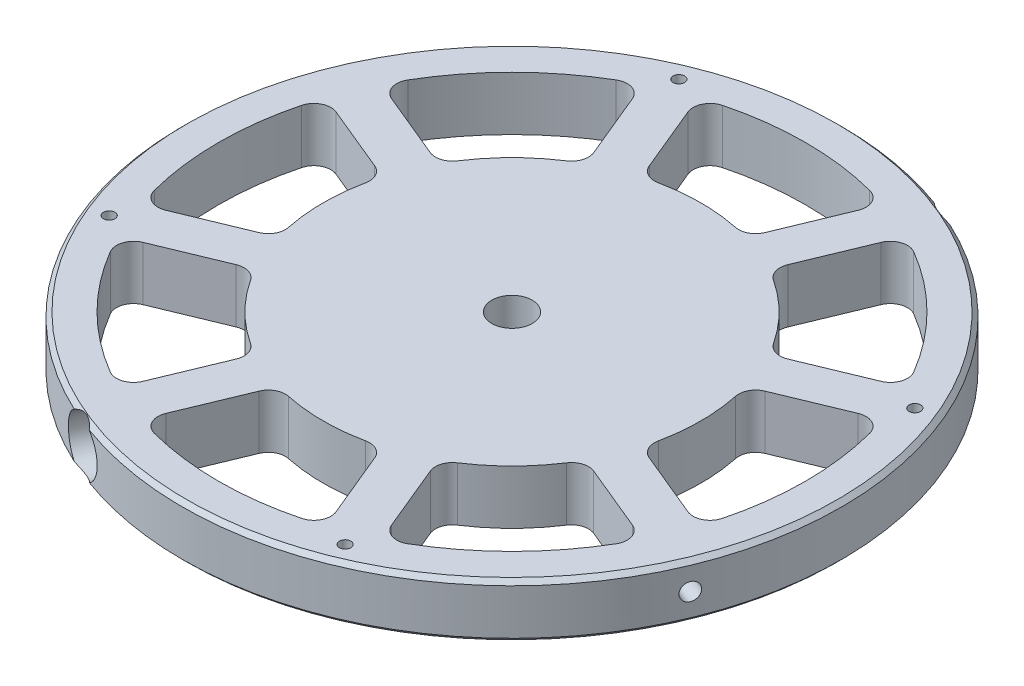
SolidWorks part; units mm, degrees
material "6061-T6 (SS)"
ref_plane "Front Plane" through (0, 0, 0) normal (0, 0, 1) x (1, 0, 0)
ref_plane "Top Plane" through (0, 0, 0) normal (0, 1, 0) x (1, 0, 0)
ref_plane "Right Plane" through (0, 0, 0) normal (1, 0, 0) x (0, 0, -1)
sketch "Sketch2" plane through (0, 0, 0) normal (1, 0, 0) x (0, 0, -1)
  line L0 (0, 0) -> (-77.55, 0)
  line L1 (-77.55, 0) -> (-77.55, 12.7)
  line L2 (-77.55, 12.7) -> (0, 12.7)
  line L5 (0, 12.7) -> (0, 0)
  dimension "D1" = 77.55
  dimension "D2" = 12.7
ref_axis "Axis1" through (0, -0.75, 0) along (0, 1, 0)
revolve "Revolve1" add sketch "Sketch2" angle 360 about axis through (0, -0.75, 0) along (0, 1, 0)
hole_wizard "#6-32 Tapped Hole2" positions "Sketch6" profile "Sketch7" tap size "#6-32" standard "ANSI Inch" end condition through all
sketch "Sketch6" plane through (0, 12.7, 0) normal (0, 1, 0) x (1, 0, 0)
  line L0 (0, 0) -> (-53.438, 129.0108) construction
  line L2 (0, 0) -> (0, 109.0908) construction
  point P0 (-27.7637, 67.0275)
  dimension "D1" = 22.5
  dimension "D2" = 72.55
sketch "Sketch7" plane through (-27.7637, 12.7, -67.0275) normal (1, 0, 0) x (0, 0, 1)
  line L0 (0, 0) -> (0, 12.7)
  line L1 (0, 12.7) -> (1.3525, 12.7)
  line L2 (1.3525, 12.7) -> (1.3525, 0)
  line L5 (1.3525, 0) -> (0, 0)
  line L11 (0, -6.35) -> (0, 107.95) construction
  dimension "Thread Major Dia." = 2.7051
  dimension "Thru Tap Drill Depth" = 12.7
pattern_circular "CirPattern3" count 4 over 360 about axis through (0, -0.75, 0) along (0, 1, 0) of "#6-32 Tapped Hole2"
sketch "Sketch8" plane through (0, 12.7, 0) normal (0, 1, 0) x (1, 0, 0)
  line L4 (0, 0) -> (0, 93.9995) construction
  line L5 (0, 0) -> (113.8372, 0) construction
  line L6 (-12.2829, 42.7192) -> (-21.7355, 65.5398)
  line L7 (12.2829, 42.7192) -> (21.7355, 65.5398)
  line L8 (0, 0) -> (-27.7637, 67.0275) construction
  arc A0 (-12.2829, 42.7192) -> (12.2829, 42.7192) centre (0, 0) cw
  arc A1 (-21.7355, 65.5398) -> (21.7355, 65.5398) centre (0, 0) cw
  circle A2 centre (0, 0) radius 77.55 construction
  dimension "D1" = 44.45
  dimension "D2" = 8.5
  dimension "D3" = 5
extrude "Cut-Extrude1" cut sketch "Sketch8" against normal through all
fillet "Fillet1" radius 4 4 edges at (12.2829, 6.35, -42.7192) (21.7355, 6.35, -65.5398) (-12.2829, 6.35, -42.7192) (-21.7355, 6.35, -65.5398)
pattern_circular "CirPattern4" count 8 over 360 about axis through (0, -0.75, 0) along (0, 1, 0) of "Cut-Extrude1", "Fillet1"
chamfer "Chamfer1" distance 1 angle 45 2 edges at (0, 0, -77.55) (0, 12.7, -77.55)
ref_plane "Plane1" through (0, 0, 0) normal (0.9239, 0, 0.3827) x (0, 1, 0)
hole_wizard "#20 (0.161) Diameter Hole1" positions "Sketch16" profile "Sketch15" hole size "#20" standard "ANSI Inch" end condition through all
sketch "Sketch16" plane through (0, 0, 0) normal (0.9239, 0, 0.3827) x (0, 1, 0)
  point P0 (6.35, 0)
  dimension "D1" = 6.35
sketch "Sketch15" plane through (0, 6.35, 0) normal (0, 1, 0) x (-0.3827, 0, 0.9239)
  line L0 (0, 0) -> (0, 101.324)
  line L1 (0, 101.324) -> (2.0447, 101.324)
  line L2 (2.0447, 101.324) -> (2.0447, 0)
  line L5 (2.0447, 0) -> (0, 0)
  line L11 (0, -6.35) -> (0, 107.95) construction
  dimension "Thru Hole Dia." = 4.0894
  dimension "Thru Hole Depth" = 101.324
ref_plane "Plane2" through (29.6771, 0, -71.6469) normal (0.3827, 0, -0.9239) x (-0.9239, 0, -0.3827)
sketch "Sketch19" plane through (29.6771, 0, -71.6469) normal (0.3827, 0, -0.9239) x (-0.9239, 0, -0.3827)
  line L0 (-76.55, 0) -> (76.55, 0) construction
  line L2 (0, -0.75) -> (0, 15.75) construction
  circle A0 centre (0, 6.35) radius 5.5625 construction
  circle A1 centre (0, 6.35) radius 6.25
  dimension "D1" = 12.5
  dimension "D2" = 6.35
extrude "Cut-Extrude3" cut sketch "Sketch19" against normal blind 5
pattern_circular "CirPattern5" count 2 over 360 about axis through (0, -0.75, 0) along (0, 1, 0) of "Cut-Extrude3"
hole_wizard "#10-24 Tapped Hole1" positions "Sketch20" profile "Sketch21" tap size "#10-24" standard "ANSI Inch"
sketch "Sketch20" plane through (-27.7637, 0, 67.0275) normal (-0.3827, 0, 0.9239) x (0.9239, 0, 0.3827)
  circle A0 centre (0, 6.35) radius 6.25
  circle A1 centre (0, 6.35) radius 6.25 construction
  point P0 (0, 6.35)
sketch "Sketch21" plane through (-27.7637, 6.35, 67.0275) normal (0, 1, 0) x (0.9239, 0, 0.3827)
  line L0 (0, 0) -> (0, 51.9408)
  line L1 (0, 51.9408) -> (1.8986, 50.8)
  line L2 (1.8986, 50.8) -> (1.8986, 0)
  line L5 (1.8986, 0) -> (0, 0)
  line L10 (0, 51.9408) -> (-1.8986, 50.8) construction
  line L11 (0, -6.35) -> (0, 107.95) construction
  dimension "Tap Drill Dia." = 3.7973
  dimension "Tap Drill Depth" = 50.8
  dimension "Drill Angle" = 118
pattern_circular "CirPattern6" count 2 over 360 about axis through (0, -0.75, 0) along (0, 1, 0) of "#10-24 Tapped Hole1"
sketch "Sketch22" plane through (0, 12.7, 0) normal (0, 1, 0) x (1, 0, 0)
  circle A0 centre (0, 0) radius 4.765
  dimension "D1" = 9.53
extrude "Cut-Extrude4" cut sketch "Sketch22" against normal blind 12.8
equation "\"TubeDiameter\" = 6.500in"
equation "\"D1@Sketch2\"=(\"TubeDiameter\"/2)-5mm"
equation "\"D2@Sketch6\"=\"TubeDiameter\"/2-10mm"
